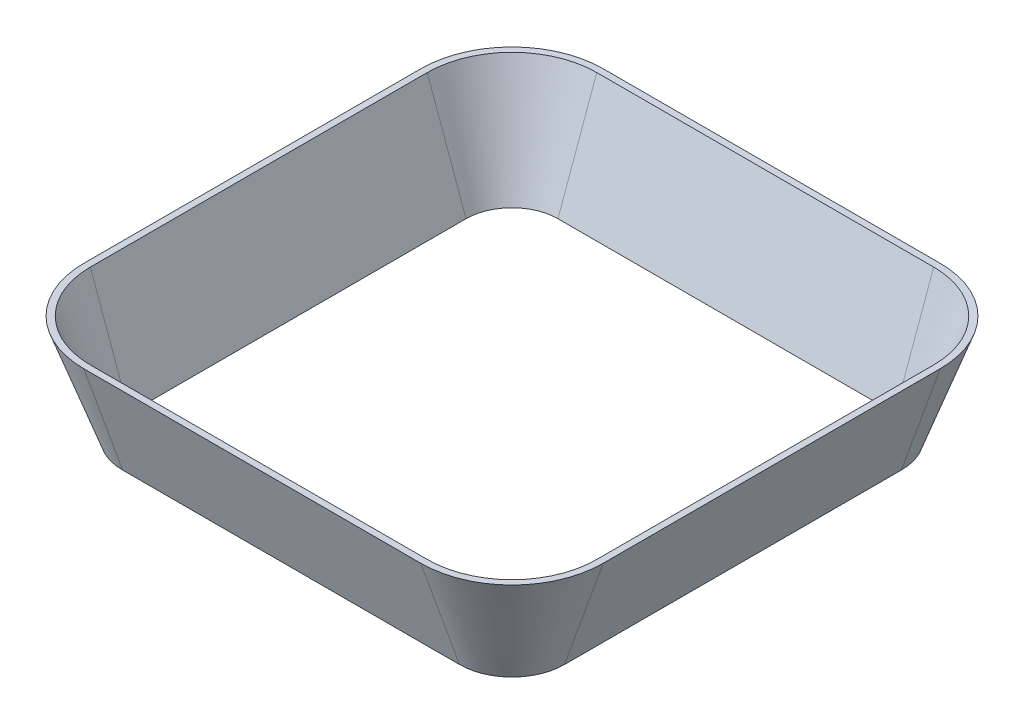
SolidWorks part; units mm, degrees
ref_plane "前视基准面" through (0, 0, 0) normal (0, 0, 1) x (1, 0, 0)
ref_plane "上视基准面" through (0, 0, 0) normal (0, 1, 0) x (1, 0, 0)
ref_plane "右视基准面" through (0, 0, 0) normal (1, 0, 0) x (0, 0, -1)
other "Configuration Table"
ref_axis "Bin Centre" through (0, 36.7501, 0) along (0, -1, 0)
sketch "Outlet Profile" plane through (0, 0, 0) normal (0, 1, 0) x (1, 0, 0)
  line L0 (-55, -72.1271) -> (55, -72.1271)
  line L1 (72.1271, -55) -> (72.1271, 55)
  line L2 (55, 72.1271) -> (-55, 72.1271)
  line L3 (-72.1271, 55) -> (-72.1271, -55)
  line L4 (-55, -55) -> (55, 55) construction
  arc A0 (55, -72.1271) -> (72.1271, -55) centre (55, -55) ccw
  arc A1 (72.1271, 55) -> (55, 72.1271) centre (55, 55) ccw
  arc A2 (-55, 72.1271) -> (-72.1271, 55) centre (-55, 55) ccw
  arc A3 (-72.1271, -55) -> (-55, -72.1271) centre (-55, -55) ccw
  point P12 (0, 0)
  dimension "CornerRadius" = 17.1271
  dimension "StraightLength" = 110
ref_plane "Inlet Height" through (0, 35, 0) normal (0, 1, 0) x (1, 0, 0)
sketch "Inlet Profile" plane through (0, 35, 0) normal (0, 1, 0) x (1, 0, 0)
  line L0 (-55, -84.8) -> (55, -84.8)
  line L1 (84.8, -55) -> (84.8, 55)
  line L2 (55, 84.8) -> (-55, 84.8)
  line L3 (-84.8, 55) -> (-84.8, -55)
  line L4 (-55, -55) -> (55, 55) construction
  arc A0 (55, -84.8) -> (84.8, -55) centre (55, -55) ccw
  arc A1 (84.8, 55) -> (55, 84.8) centre (55, 55) ccw
  arc A2 (-55, 84.8) -> (-84.8, 55) centre (-55, 55) ccw
  arc A3 (-84.8, -55) -> (-55, -84.8) centre (-55, -55) ccw
  point P12 (0, 0)
  dimension "CornerRadius" = 29.8
  dimension "StraightLength" = 110
loft "Hopper Shape" add profiles "Outlet Profile", "Inlet Profile"
shell "Wall Thickness" thickness 2 removed face at (0, 35, 0) removed face at (0, 0, 0)
